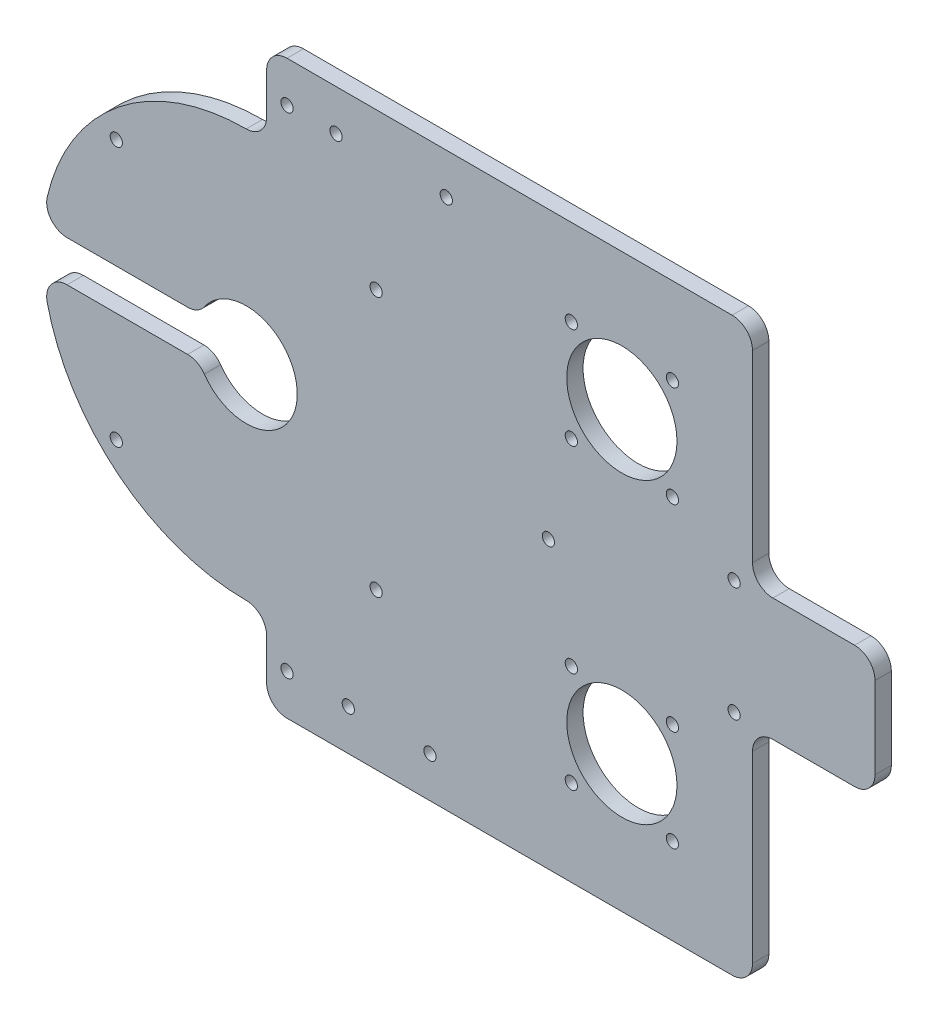
SolidWorks part; units mm, degrees
ref_plane "前视基准面" through (0, 0, 0) normal (0, 0, 1) x (1, 0, 0)
ref_plane "上视基准面" through (0, 0, 0) normal (0, 1, 0) x (1, 0, 0)
ref_plane "右视基准面" through (0, 0, 0) normal (1, 0, 0) x (0, 0, -1)
other "Configuration Table"
sketch "草图1" plane through (0, 0, 0) normal (0, 0, 1) x (1, 0, 0)
  line L1 (-55, 50) -> (55, 50)
  line L2 (-55, 50) -> (-55, -50)
  line L3 (-55, -50) -> (55, -50)
  line L4 (55, 50) -> (55, -50)
  line L5 (-55, 50) -> (55, -50) construction
  line L6 (-55, -50) -> (55, 50) construction
  line L7 (119, 70) -> (55, 70)
  line L8 (119, 70) -> (119, -70)
  line L9 (119, -70) -> (55, -70)
  line L10 (55, 70) -> (55, -70)
  line L11 (119, 70) -> (55, -70) construction
  line L12 (119, -70) -> (55, 70) construction
  line L13 (149, 15) -> (119, 15)
  line L14 (149, 15) -> (149, -15)
  line L15 (149, -15) -> (119, -15)
  line L16 (119, 15) -> (119, -15)
  line L17 (149, 15) -> (119, -15) construction
  line L18 (149, -15) -> (119, 15) construction
  line L19 (55, 50) -> (0, 50)
  line L20 (55, 50) -> (55, 70)
  line L21 (55, 70) -> (0, 70)
  line L22 (0, 50) -> (0, 70)
  line L23 (55, -50) -> (0, -50)
  line L24 (55, -50) -> (55, -70)
  line L25 (55, -70) -> (0, -70)
  line L26 (0, -50) -> (0, -70)
  point P0 (0, 0)
  point P6 (87, 0)
  point P11 (134, 0)
  dimension "D1" = 100
  dimension "D2" = 110
  dimension "D3" = 64
  dimension "D4" = 140
  dimension "D5" = 30
  dimension "D6" = 30
extrude "凸台-拉伸1" add sketch "草图1" along normal blind 4 contours L4 L1 L2 L3 | L7 L10 L4 L9 L8 | L15 L14 L13 L8 region at (0, 0, 0) region at (87, 0, 0) region at (134, 0, 0)
fillet "圆角1" radius 50 2 edges at (-55, -50, 2) (-55, 50, 2)
sketch "草图2" plane through (0, 0, 4) normal (0, 0, 1) x (1, 0, 0)
  line L0 (119, 70) -> (55, 70) construction
  line L1 (74.6256, 48.8744) -> (87, 36.5) construction
  line L2 (-27.5, 5) -> (-7.5, 5)
  line L3 (-27.5, 5) -> (-27.5, -5)
  line L4 (-27.5, -5) -> (-7.5, -5)
  line L5 (-7.5, 5) -> (-7.5, -5)
  line L6 (-27.5, 5) -> (-7.5, -5) construction
  line L7 (-27.5, -5) -> (-7.5, 5) construction
  line L9 (55, 70) -> (55, 50) construction
  line L10 (-27.5, -5) -> (-85.654, -5)
  line L11 (-27.5, -5) -> (-27.5, 5)
  line L12 (-27.5, 5) -> (-85.654, 5)
  line L13 (-85.654, -5) -> (-85.654, 5)
  circle A0 centre (-5, 0) radius 12.5
  circle A1 centre (87, 36.5) radius 13.5
  circle A2 centre (87, -36.5) radius 13.5
  circle A3 centre (74.6256, 48.8744) radius 1.5
  circle A4 centre (99.3744, 48.8744) radius 1.5
  circle A5 centre (99.3744, 24.1256) radius 1.5
  circle A6 centre (74.6256, 24.1256) radius 1.5
  circle A7 centre (74.6256, -24.1256) radius 1.5
  circle A8 centre (99.3744, -24.1256) radius 1.5
  circle A9 centre (99.3744, -48.8744) radius 1.5
  circle A10 centre (74.6256, -48.8744) radius 1.5
  point P7 (-17.5, 0)
  point P10 (87, 70)
  arc M1 (-5, 50) -> (-55, 0) centre (-5, 0) ccw
  arc M2 (-55, 0) -> (-5, -50) centre (-5, 0) ccw
  dimension "D1" = 25
  dimension "D4" = 27
  dimension "D5" = 27
  dimension "D8" = 3
  dimension "D13" = 3
  dimension "D2" = 73
  dimension "D3" = 36.5
  dimension "D6" = 10
  dimension "D7" = 20
  dimension "D9" = 17.5
  dimension "D10" = 45
  dimension "D12" = 17.5
  dimension "D15" = 58.154
  dimension "D11" = 4
  dimension "D14" = 4
extrude "切除-拉伸1" cut sketch "草图2" against normal blind 4 contours L4 A0 L2 L5 | L2 A0 L4 L5 | A0 L2 L3 L4 | A1 | A5 | A6 | A3 | A4 | A2 | A7 | A8 | A9 | L13 L10 L12 M2 M1 | L3 L12 L10 M1 M2 | A10 region at (-22.3245, 0, 4) region at (-41.2084, 0, 4) region at (-3.2035, 0, 4) region at (-12.334, 0, 4) region at (-70.2852, 0, 4) region at (87, 36.5, 4) region at (87, -36.5, 4) region at (74.6256, 48.8744, 4) region at (99.3744, 48.8744, 4) region at (99.3744, 24.1256, 4) region at (74.6256, 24.1256, 4) region at (74.6256, -24.1256, 4) region at (99.3744, -24.1256, 4) region at (99.3744, -48.8744, 4)
sketch "草图4" plane through (0, 0, 4) normal (0, 0, 1) x (1, 0, 0)
  line L0 (119, -70) -> (55, -70) construction
  line L1 (55, 50) -> (0, 50)
  line L2 (55, 50) -> (55, 70)
  line L3 (55, 70) -> (0, 70)
  line L4 (0, 50) -> (0, 70)
  line L5 (55, -50) -> (0, -50)
  line L6 (55, -50) -> (55, -70)
  line L7 (55, -70) -> (0, -70)
  line L8 (0, -50) -> (0, -70)
  line L9 (119, 70) -> (55, 70) construction
extrude "凸台-拉伸2" add sketch "草图4" against normal blind 4
fillet "圆角2" radius 5 14 edges at (0, -70, 2) (119, -70, 2) (119, -15, 2) (149, -15, 2) (149, 15, 2) (119, 15, 2) (119, 70, 2) (0, 50, 2) (-54.7494, 5, 2) (-16.4564, 5, 2) (-16.4564, -5, 2) (-54.7494, -5, 2) (0, -50, 2) (0, 70, 2)
sketch "草图5" plane through (0, 0, 4) normal (0, 0, 1) x (1, 0, 0)
  line L0 (119, 65) -> (119, 20) construction
  line L1 (0, -55) -> (0, -65) construction
  line L2 (-36.8198, 31.8198) -> (26.8198, 31.8198) construction
  line L3 (-36.8198, 31.8198) -> (-36.8198, -31.8198) construction
  line L4 (-36.8198, -31.8198) -> (26.8198, -31.8198) construction
  line L5 (26.8198, 31.8198) -> (26.8198, -31.8198) construction
  line L6 (-36.8198, 31.8198) -> (26.8198, -31.8198) construction
  line L7 (-36.8198, -31.8198) -> (26.8198, 31.8198) construction
  line L8 (114, -70) -> (5, -70) construction
  line L9 (0, 65) -> (0, 55) construction
  line L10 (114, 70) -> (5, 70) construction
  circle A0 centre (114.5, 14) radius 1.5
  circle A1 centre (114.5, -14) radius 1.5
  circle A2 centre (69, 0) radius 1.5
  arc A3 (-15.2581, -7.1429) -> (-15.2581, 7.1429) centre (-5, 0) ccw construction
  arc A4 (-15.2581, -7.1429) -> (-15.2581, 7.1429) centre (-5, 0) ccw construction
  circle A5 centre (-36.8198, 31.8198) radius 1.5
  circle A6 centre (26.8198, 31.8198) radius 1.5
  circle A7 centre (26.8198, -31.8198) radius 1.5
  circle A8 centre (-36.8198, -31.8198) radius 1.5
  circle A9 centre (5, -60) radius 1.5
  circle A10 centre (20, -60) radius 1.5
  circle A11 centre (40, -60) radius 1.5
  circle A12 centre (5, 60) radius 1.5
  circle A13 centre (17, 60) radius 1.5
  circle A14 centre (44, 60) radius 1.5
  point P40 (0, 0)
  dimension "D2" = 3
  dimension "D3" = 3
  dimension "D4" = 3
  dimension "D9" = 3
  dimension "D10" = 3
  dimension "D11" = 3
  dimension "D12" = 3
  dimension "D13" = 3
  dimension "D14" = 3
  dimension "D15" = 3
  dimension "D24" = 3
  dimension "D25" = 3
  dimension "D26" = 3
  dimension "D1" = 45.5
  dimension "D5" = 28
  dimension "D6" = 14
  dimension "D7" = 4.5
  dimension "D8" = 90
  dimension "D16" = 5
  dimension "D17" = 15
  dimension "D18" = 20
  dimension "D19" = 10
  dimension "D20" = 5
  dimension "D21" = 12
  dimension "D22" = 27
  dimension "D23" = 10
extrude "切除-拉伸2" cut sketch "草图5" against normal up to vertex (4 mm away) up to point (0, 0, 0)
